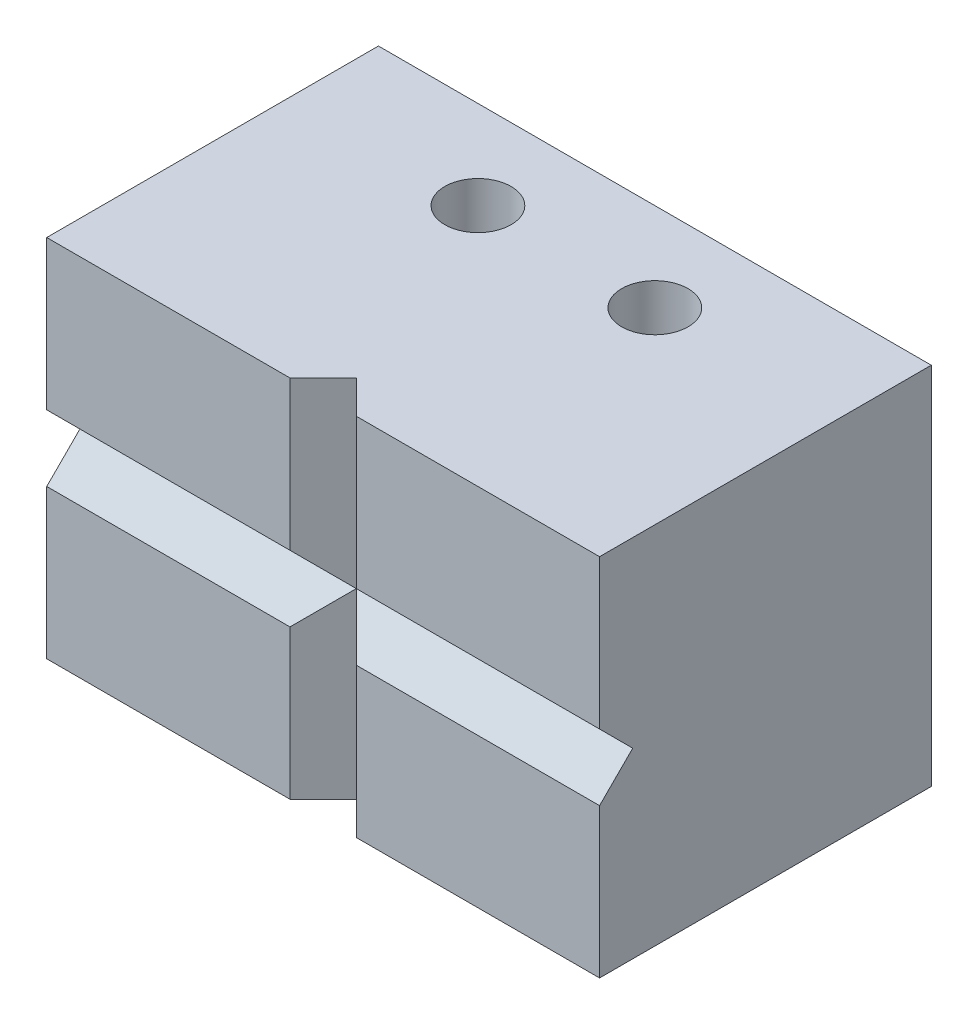
SolidWorks part; units mm, degrees
ref_plane "Front Plane" through (0, 0, 0) normal (0, 0, 1) x (1, 0, 0)
ref_plane "Top Plane" through (0, 0, 0) normal (0, 1, 0) x (1, 0, 0)
ref_plane "Right Plane" through (0, 0, 0) normal (1, 0, 0) x (0, 0, -1)
sketch "Sketch1" plane through (0, 0, 0) normal (0, 1, 0) x (1, 0, 0)
  line L0 (-15.7823, 0) -> (15.7823, 0) construction
  line L1 (12.5, -7.5) -> (1.5, -7.5)
  line L2 (12.5, -7.5) -> (12.5, 7.5)
  line L3 (12.5, 7.5) -> (-12.5, 7.5)
  line L4 (-12.5, -7.5) -> (-12.5, 7.5)
  line L5 (12.5, -7.5) -> (-12.5, 7.5) construction
  line L6 (12.5, 7.5) -> (-12.5, -7.5) construction
  line L7 (0, -11.8811) -> (0, 11.8811) construction
  line L8 (-1.5, -7.5) -> (0, -6)
  line L9 (1.5, -7.5) -> (0, -6)
  line L10 (-1.5, -7.5) -> (-12.5, -7.5)
  circle A0 centre (-4, 3.5) radius 1.5
  circle A1 centre (4, 3.5) radius 1.5
  point P0 (0, 0)
  point P9 (0, 0)
  point P12 (0, 0)
  dimension "D3" = 3
  dimension "D1" = 15
  dimension "D2" = 11
  dimension "D4" = 8
  dimension "D5" = 25
  dimension "D6" = 3
  dimension "D7" = 1.5
extrude "Boss-Extrude1" add sketch "Sketch1" along normal blind 15 and the other way blind 1.5
sketch "Sketch3" plane through (12.5, 0, 0) normal (1, 0, 0) x (0, 0, -1)
  line L0 (-7.5, 6.75) -> (7.5, 6.75) construction
  line L1 (-7.5, 15) -> (-7.5, -1.5) construction
  line L2 (7.5, 15) -> (7.5, -1.5) construction
  line L3 (-7.5, 8.25) -> (-6, 6.75)
  line L4 (-7.5, 5.25) -> (-6, 6.75)
  line L5 (-7.5, 8.25) -> (-7.5, 5.25)
  dimension "D1" = 3
  dimension "D2" = 1.5
extrude "Cut-Extrude1" cut sketch "Sketch3" against normal up to surface (25 mm away) up to face at (-12.5, 6.75, 0)
hole_wizard "Ø8.0mm Dowel Hole1" [suppressed] positions "Sketch4" profile "Sketch5" hole size "Ø8.0" standard "ANSI Metric"
sketch "Sketch4" plane through (12.5, 0, 0) normal (1, 0, 0) x (0, 0, -1)
  point P7 (0, 7.5)
sketch "Sketch5" plane through (12.5, 7.5, 0) normal (0, 1, 0) x (0, 0, -1)
  line L0 (0, 0) -> (0, 11.4034)
  line L1 (0, 11.4034) -> (4, 9)
  line L2 (4, 9) -> (4, 0)
  line L5 (4, 0) -> (0, 0)
  line L10 (0, 11.4034) -> (-4, 9) construction
  line L11 (0, -6.35) -> (0, 107.95) construction
  dimension "Hole Dia." = 8
  dimension "Hole Depth" = 9
  dimension "Drill Angle" = 118
thread "Thread1" [suppressed] pitch 1 start angle 0, offset 1, length 0, pitch 1, diameter 8
ref_plane "Plane1" through (13.5, 7.5, 4) normal (0, -1, 0) x (0, 0, 1)
sketch "Thread Profile1" plane through (13.5, 7.5, 4) normal (0, -1, 0) x (0, 0, 1)
  line L0 (0, 0) -> (0, 1) construction
  line L11 (0, 0) -> (0, 0.875)
  line L12 (0, 0.875) -> (-0.5413, 0.5625)
  line L13 (-0.5413, 0.5625) -> (-0.5413, 0.3125)
  line L15 (-0.5413, 0.3125) -> (0, 0)
  line L17 (-0.5413, 0.4375) -> (0, 0.4375) construction
  point P2 (0, 0)
  dimension "Pitch" = 1
  dimension "Profile_Angle" = 60
  dimension "Profile_Land" = 0.25
  dimension "Profile_Height" = 0.5413
hole_wizard "Ø8.0mm Dowel Hole3" positions "Sketch7" profile "Sketch8" hole size "Ø8.0" standard "ANSI Metric"
sketch "Sketch7" plane through (0, 0, -7.5) normal (0, 0, -1) x (-1, 0, 0)
  point P0 (0, 6.75)
sketch "Sketch8" plane through (0, 6.75, -7.5) normal (1, 0, 0) x (0, 1, 0)
  line L0 (0, 0) -> (0, 11.4034)
  line L1 (0, 11.4034) -> (4, 9)
  line L2 (4, 9) -> (4, 0)
  line L5 (4, 0) -> (0, 0)
  line L10 (0, 11.4034) -> (-4, 9) construction
  line L11 (0, -6.35) -> (0, 107.95) construction
  dimension "Hole Dia." = 8
  dimension "Hole Depth" = 9
  dimension "Drill Angle" = 118
thread "Thread2" pitch 1 start angle 0, offset 1, length 0, pitch 1, diameter 8
ref_plane "Plane2" through (4, 6.75, -8.5) normal (0, -1, 0) x (1, 0, 0)
sketch "Thread Profile2" plane through (4, 6.75, -8.5) normal (0, -1, 0) x (1, 0, 0)
  line L0 (0, 0) -> (0, 1) construction
  line L11 (0, 0) -> (0, 0.875)
  line L12 (0, 0.875) -> (-0.5413, 0.5625)
  line L13 (-0.5413, 0.5625) -> (-0.5413, 0.3125)
  line L15 (-0.5413, 0.3125) -> (0, 0)
  line L17 (-0.5413, 0.4375) -> (0, 0.4375) construction
  point P2 (0, 0)
  dimension "Pitch" = 1
  dimension "Profile_Angle" = 60
  dimension "Profile_Land" = 0.25
  dimension "Profile_Height" = 0.5413
